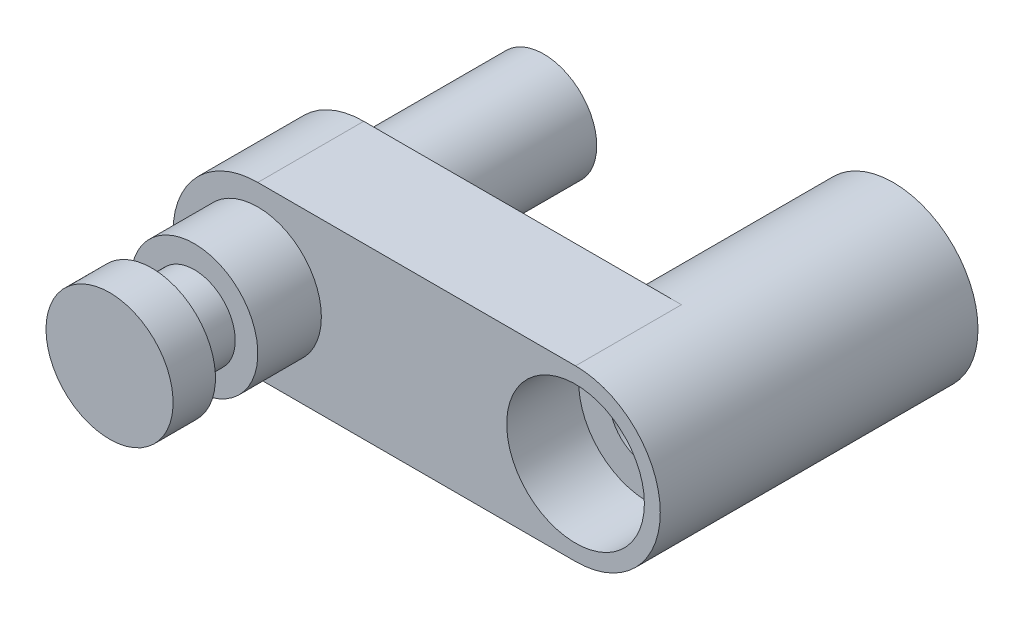
SolidWorks part; units mm, degrees
note: The reader was unsure of these and kept them because the rebuilt part matched: shared geometry of "Sketch2<3>".
ref_plane "Ebene vorne" through (0, 0, 0) normal (0, 0, 1) x (1, 0, 0)
ref_plane "Ebene oben" through (0, 0, 0) normal (0, 1, 0) x (1, 0, 0)
ref_plane "Ebene rechts" through (0, 0, 0) normal (1, 0, 0) x (0, 0, -1)
sketch "Sketch1" plane through (0, 0, 0) normal (0, 0, 1) x (1, 0, 0)
  circle A0 centre (0, 0) radius 4
  dimension "D1" = 8
extrude "Boss-Extrude1" add sketch "Sketch1" along normal blind 10
sketch "Sketch2" plane through (0, 0, 10) normal (0, 0, 1) x (1, 0, 0)
  line L0 (-15, 4) -> (0, 4)
  line L1 (-15, -4) -> (0, -4)
  line L2 (-15, 0) -> (0, 0) construction
  circle A0 centre (0, 0) radius 4
  circle A1 centre (-15, 0) radius 2.5
  circle A2 centre (-15, 0) radius 4
  dimension "D1" = 5
  dimension "D2" = 15
  dimension "D3" = 8
extrude "Boss-Extrude2" add sketch "Sketch2" along normal blind 5
extrude "Boss-Extrude3" add sketch "Sketch2<3>" against normal blind 8.5
sketch "Sketch2<3>" plane through (0, 0, 10) normal (0, 0, 1) x (1, 0, 0) same geometry as "Sketch2"
hole_wizard "CBORE for M3 Hex Socket Head Cap Screw1" positions "Sketch3" profile "Sketch4" counterbore size "M3" standard "DIN" end condition through all
sketch "Sketch3" plane through (0, 0, 15) normal (0, 0, 1) x (1, 0, 0)
  point P0 (0, 0)
sketch "Sketch4" plane through (0, 0, 15) normal (1, 0, 0) x (0, -1, 0)
  line L0 (0, 0) -> (0, 15)
  line L1 (0, 15) -> (1.8, 15)
  line L3 (1.8, 15) -> (1.8, 3.4)
  line L4 (1.8, 3.4) -> (3.25, 3.4)
  line L5 (3.25, 3.4) -> (3.25, 0)
  line L7 (3.25, 0) -> (0, 0)
  line L11 (0, -6.35) -> (0, 107.95) construction
  dimension "Thru Hole Dia." = 3.6
  dimension "Thru Hole Depth" = 15
  dimension "C'Bore Dia." = 6.5
  dimension "C'Bore Depth" = 3.4
sketch "Sketch6" plane through (0, 0, 0) normal (0, 1, 0) x (1, 0, 0)
  line L0 (-15, -10) -> (-15, -22.5815) construction
  line L1 (-15, -15) -> (-18, -15)
  line L2 (-19, -15) -> (-15, -15) construction
  line L3 (-18, -15) -> (-18, -18)
  line L4 (-18, -18) -> (-16.9348, -18)
  line L5 (-16.9348, -18) -> (-16.9348, -20)
  line L6 (-16.9348, -20) -> (-18, -20)
  line L7 (-18, -20) -> (-18, -22)
  line L8 (-18, -22) -> (-15, -22)
  line L9 (-15, -15) -> (-15, -22)
  dimension "D1" = 6
  dimension "D2" = 2
  dimension "D3" = 3
  dimension "D4" = 2
revolve "Revolve1" add sketch "Sketch6" angle 360 about L0
